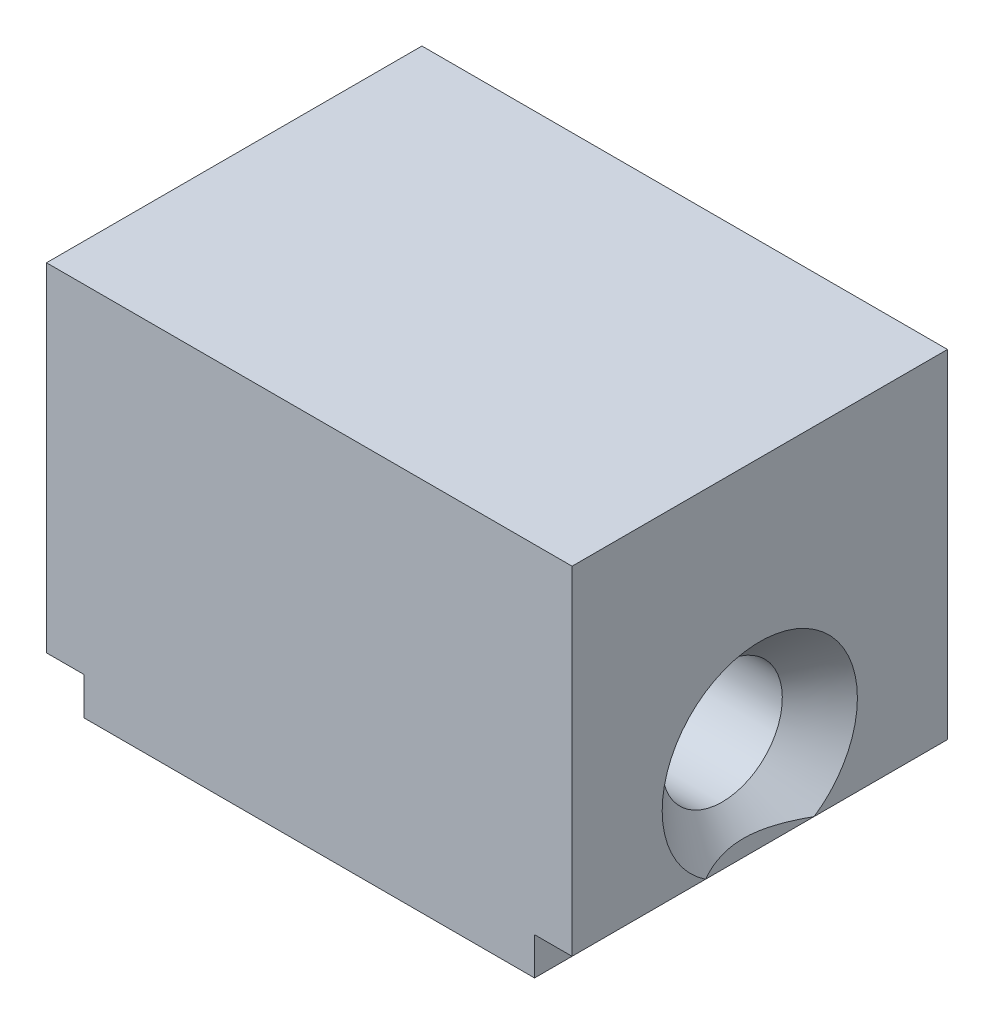
SolidWorks part; units mm, degrees
ref_plane "Front Plane" through (0, 0, 0) normal (0, 0, 1) x (1, 0, 0)
ref_plane "Top Plane" through (0, 0, 0) normal (0, 1, 0) x (1, 0, 0)
ref_plane "Right Plane" through (0, 0, 0) normal (1, 0, 0) x (0, 0, -1)
sketch "Sketch1" plane through (0, 0, 0) normal (0, 1, 0) x (1, 0, 0)
  line L1 (-3, 2.5) -> (3, 2.5)
  line L2 (-3, 2.5) -> (-3, -2.5)
  line L3 (-3, -2.5) -> (3, -2.5)
  line L4 (3, 2.5) -> (3, -2.5)
  line L5 (-3, 2.5) -> (3, -2.5) construction
  line L6 (-3, -2.5) -> (3, 2.5) construction
  point P0 (0, 0)
  dimension "D1" = 6
  dimension "D2" = 5
extrude "Boss-Extrude1" add sketch "Sketch1" along normal blind 0.5
sketch "Sketch2" plane through (0, 0.5, 0) normal (0, 1, 0) x (1, 0, 0)
  line L1 (-3.5, -2.5) -> (3.5, -2.5)
  line L2 (-3.5, -2.5) -> (-3.5, 2.5)
  line L3 (-3.5, 2.5) -> (3.5, 2.5)
  line L4 (3.5, -2.5) -> (3.5, 2.5)
  line L5 (-3.5, -2.5) -> (3.5, 2.5) construction
  line L6 (-3.5, 2.5) -> (3.5, -2.5) construction
  point P0 (0, 0)
  dimension "D1" = 5
  dimension "D2" = 7
extrude "Boss-Extrude2" add sketch "Sketch2" along normal blind 4.5
sketch "Sketch3" plane through (-3.5, 0, 0) normal (-1, 0, 0) x (0, 0, 1)
  line L0 (0, 0) -> (0, 5) construction
  line L1 (-2.5, 5) -> (2.5, 5) construction
  circle A0 centre (0, 1.58) radius 0.8
  point P7 (0, 1.3458)
  dimension "D2" = 1.6
  dimension "D1" = 1.58
extrude "Cut-Extrude1" cut sketch "Sketch3" against normal through all
chamfer "Chamfer1" distance 0.5 angle 45 2 edges at (3.5, 1.58, 0.8) (-3.5, 1.58, 0.8)
